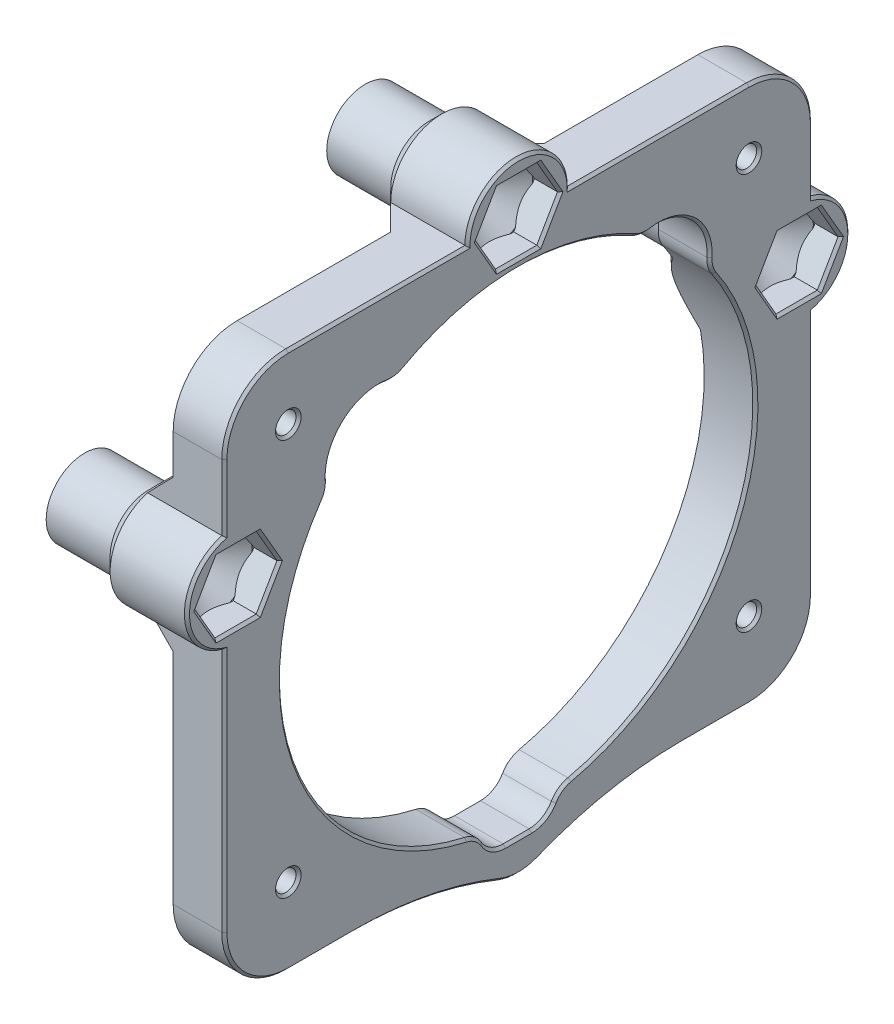
SolidWorks part; units mm, degrees
ref_plane "前视基准面" through (0, 0, 0) normal (0, 0, 1) x (1, 0, 0)
ref_plane "上视基准面" through (0, 0, 0) normal (0, 1, 0) x (1, 0, 0)
ref_plane "右视基准面" through (0, 0, 0) normal (1, 0, 0) x (0, 0, -1)
other "Configuration Table"
sketch "草图1" plane through (0, 0, 0) normal (1, 0, 0) x (0, 0, -1)
  line L1 (0, 0) -> (46, 0)
  line L2 (0, 0) -> (0, -41)
  line L3 (0, -41) -> (46, -41)
  line L4 (46, 0) -> (46, -41)
  circle A0 centre (5, -5) radius 0.8
  circle A1 centre (41, -5) radius 0.8
  circle A2 centre (5, -36) radius 0.8
  circle A3 centre (41, -36) radius 0.8
  dimension "D1" = 1.6
  dimension "D2" = 1.6
  dimension "D3" = 1.6
  dimension "D4" = 1.6
  dimension "D7" = 46
  dimension "D8" = 41
  dimension "D5" = 5
  dimension "D6" = 5
  dimension "D9" = 5
  dimension "D10" = 5
  dimension "D11" = 5
  dimension "D12" = 5
  dimension "D13" = 5
  dimension "D14" = 5
extrude "凸台-拉伸1" add sketch "草图1" along normal blind 4
sketch "草图2" plane through (0, 0, 0) normal (-1, 0, 0) x (0, 0, 1)
  line L1 (-46, 0) -> (0, 0) construction
  circle A0 centre (-44.925, -14) radius 4
  circle A1 centre (-1.075, -14) radius 4
  circle A2 centre (-23, 0) radius 4
  point P8 (-23, 0)
  dimension "D7" = 8
  dimension "D8" = 8
  dimension "D9" = 8
  dimension "D2" = 0
  dimension "D3" = 14
  dimension "D4" = 14
  dimension "D5" = 43.85
  dimension "D6" = 21.925
extrude "凸台-拉伸2" add sketch "草图2" against normal blind 4
sketch "草图3" plane through (0, 0, 0) normal (-1, 0, 0) x (0, 0, 1)
  circle A0 centre (-44.925, -14) radius 3
  circle A1 centre (-23, 0) radius 3
  circle A2 centre (-1.075, -14) radius 3
  dimension "D1" = 6
  dimension "D2" = 6
  dimension "D3" = 6
extrude "凸台-拉伸3" add sketch "草图3" along normal blind 8
sketch "草图4" plane through (-8, 0, 0) normal (-1, 0, 0) x (0, 0, 1)
  circle A0 centre (-44.925, -14) radius 1.6
  circle A1 centre (-23, 0) radius 1.6
  circle A2 centre (-1.075, -14) radius 1.6
  dimension "D1" = 3.2
  dimension "D2" = 3.2
  dimension "D3" = 3.2
extrude "切除-拉伸2" cut sketch "草图4" against normal through all
sketch "草图5" plane through (4, 0, 0) normal (1, 0, 0) x (0, 0, -1)
  line L1 (4.3082, -14) -> (2.6916, -11.2)
  line L2 (2.6916, -11.2) -> (-0.5416, -11.2)
  line L3 (-0.5416, -11.2) -> (-2.1582, -14)
  line L4 (-2.1582, -14) -> (-0.5416, -16.8)
  line L5 (-0.5416, -16.8) -> (2.6916, -16.8)
  line L6 (2.6916, -16.8) -> (4.3082, -14)
  line L7 (26.2332, 0) -> (24.6166, 2.8)
  line L8 (24.6166, 2.8) -> (21.3834, 2.8)
  line L9 (21.3834, 2.8) -> (19.7668, 0)
  line L10 (19.7668, 0) -> (21.3834, -2.8)
  line L11 (21.3834, -2.8) -> (24.6166, -2.8)
  line L12 (24.6166, -2.8) -> (26.2332, 0)
  line L13 (48.1582, -14) -> (46.5416, -11.2)
  line L14 (46.5416, -11.2) -> (43.3084, -11.2)
  line L15 (43.3084, -11.2) -> (41.6918, -14)
  line L16 (41.6918, -14) -> (43.3084, -16.8)
  line L17 (43.3084, -16.8) -> (46.5416, -16.8)
  line L18 (46.5416, -16.8) -> (48.1582, -14)
  circle A3 centre (1.075, -14) radius 2.8 construction
  circle A4 centre (23, 0) radius 2.8 construction
  circle A5 centre (44.925, -14) radius 2.8 construction
  dimension "D1" = 5.6
  dimension "D2" = 5.6
  dimension "D3" = 5.6
extrude "切除-拉伸3" cut sketch "草图5" against normal blind 2
chamfer "倒角2" distance 3 angle 45 3 edges at (0, -14, -4.075) (0, 0, -26) (0, -14, -47.925)
sketch "草图6" plane through (0, 0, 0) normal (-1, 0, 0) x (0, 0, 1)
  circle A0 centre (-23, -22) radius 18.5
  dimension "D1" = 37
extrude "切除-拉伸4" cut sketch "草图6" against normal through all and the other way through all
sketch "草图7" plane through (0, -41, 0) normal (0, -1, 0) x (-1, 0, 0)
  line L1 (0, 0) -> (-4, 0)
  line L2 (0, 0) -> (0, 46)
  line L3 (0, 46) -> (-4, 46)
  line L4 (-4, 0) -> (-4, 46)
extrude "凸台-拉伸4" add sketch "草图7" along normal blind 1
fillet "圆角2" radius 5 4 edges at (2, 0, 0) (2, 0, -46) (2, -42, -46) (2, -42, 0)
sketch "草图8" plane through (0, 0, 0) normal (-1, 0, 0) x (0, 0, 1)
  circle A0 centre (-33.925, -10) radius 4
  circle A1 centre (-12.075, -10) radius 4
  circle A2 centre (-44.925, -14) radius 1.6 construction
  circle A3 centre (-1.075, -14) radius 1.6 construction
  dimension "D1" = 8
  dimension "D2" = 8
  dimension "D6" = 11
  dimension "D3" = 4
  dimension "D4" = 4
  dimension "D5" = 11
extrude "切除-拉伸5" cut sketch "草图8" against normal through all
sketch "草图9" plane through (0, 0, 0) normal (-1, 0, 0) x (0, 0, 1)
  line L0 (-26.7081, -42) -> (-19.2919, -42)
  line L1 (-5, -42) -> (-41, -42) construction
  arc A0 (-26.7081, -42) -> (-19.2919, -42) centre (-23, -40.5) ccw
  arc A1 (-41.2046, -18.7073) -> (-4.7954, -18.7073) centre (-23, -22) ccw construction
  dimension "D1" = 8
extrude "凸台-拉伸5" add sketch "草图9" against normal blind 4
fillet "圆角3" radius 30 2 edges at (2, -42, -19.2919) (2, -42, -26.7081)
sketch "草图10" plane through (0, 0, 0) normal (-1, 0, 0) x (0, 0, 1)
  line L0 (-5, -42) -> (-10.2035, -42) construction
  line L1 (-26, -38.5149) -> (-20, -38.5149)
  line L2 (-26, -38.5149) -> (-26, -42)
  line L3 (-26, -42) -> (-20, -42)
  line L4 (-20, -38.5149) -> (-20, -42)
  arc A0 (-24.5055, -44.2059) -> (-21.4945, -44.2059) centre (-23, -40.5) ccw construction
  point P4 (-23, -42)
  point P8 (-23, -44.5)
  dimension "D1" = 6
  dimension "D2" = 0
  dimension "D3" = 0
extrude "切除-拉伸6" cut sketch "草图10" against normal through all
fillet "圆角4" radius 2 2 edges at (2, -42, -20) (2, -42, -26)
fillet "圆角5" radius 2 6 edges at (2, -10.9228, -37.8171) (2, -6.2113, -32.642) (2, -6.2113, -13.358) (2, -10.9228, -8.1829) (2, -40.2551, -20) (2, -40.2551, -26)
chamfer "倒角3" distance 0.2 angle 45 54 edges at (4, -36, -41.8) (4, -5, -41.8) (4, -5, -5.8) (4, -36, -5.8) (4, 4, -23) (4, 0, -34) (4, -1.4645, -44.5355) (4, -7.5736, -46) (4, -14, -48.925) (4, -27.4264, -46) (4, -40.5355, -44.5355) (4, -42, -7.6018) (4, -42, -38.3982) (4, -40.5355, -1.4645) (4, -27.4264, 0) (4, -14, 2.925) (4, -7.5736, 0) (4, -1.4645, -1.4645) (4, 0, -12) (4, -7.0422, -9.3822) (4, -7.0422, -36.6178) (4, -42.5566, -30.0442) (4, -44.5, -23) (4, -42.5566, -15.9558) (4, -10.938, -37.9811) (4, -6.0494, -32.6115) (4, -3.5, -23) (4, -6.0494, -13.3885) (4, -10.938, -8.0189) (4, -28.7749, -5.7852) (4, -28.7749, -40.2148) (4, -12.6, -47.3499) (4, -11.2, -44.925) (4, -12.6, -42.5001) (4, -15.4, -42.5001) (4, -16.8, -44.925) (4, -15.4, -47.3499) (4, 1.4, -25.4249) (4, 2.8, -23) (4, 1.4, -20.5751) (4, -1.4, -20.5751) (4, -2.8, -23) (4, -1.4, -25.4249) (4, -12.6, -3.4999) (4, -11.2, -1.075) (4, -12.6, 1.3499) (4, -15.4, 1.3499) (4, -16.8, -1.075) (4, -15.4, -3.4999) (4, -40.3925, -19.7056) (4, -41.7328, -20.9849) (4, -42, -23) (4, -41.7328, -25.0151) (4, -40.3925, -26.2944)
chamfer "倒角5" distance 1.5 angle 45 3 edges at (2, -14, -46.525) (2, 0, -24.6) (2, -14, -2.675)
equation "\"D7@草图1\"=36+10"
equation "\"D8@草图1\"=31+10"
equation "\"D6@草图2\"=\"D5@草图2\"/2"
